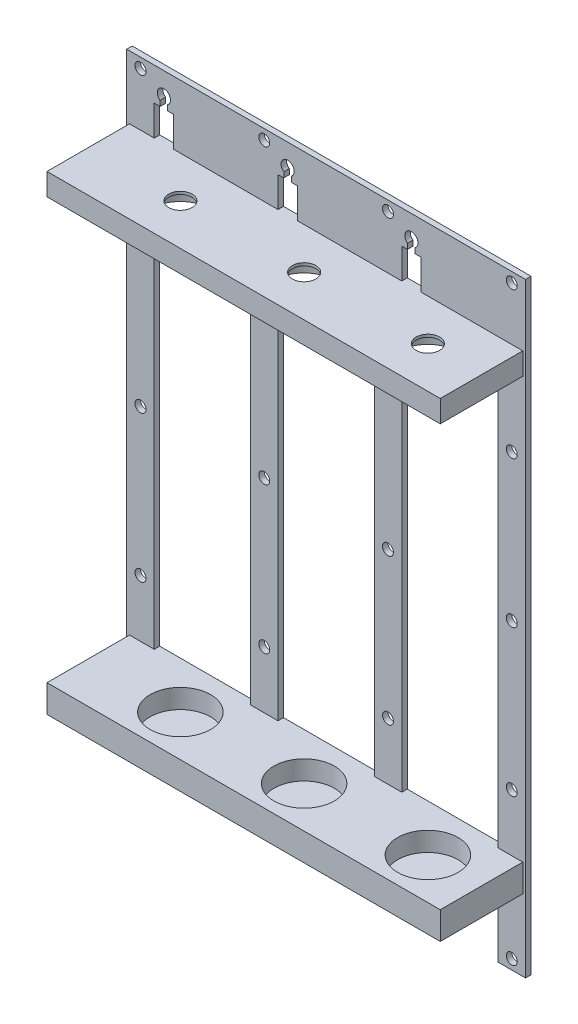
SolidWorks part; units mm, degrees
ref_plane "Płaszczyzna przednia" through (0, 0, 0) normal (0, 0, 1) x (1, 0, 0)
ref_plane "Płaszczyzna górna" through (0, 0, 0) normal (0, 1, 0) x (1, 0, 0)
ref_plane "Płaszczyzna prawa" through (0, 0, 0) normal (1, 0, 0) x (0, 0, -1)
sketch "Szkic4" plane through (0, 0, 0) normal (0, 0, 1) x (1, 0, 0)
  line L14 (-48.2384, -12) -> (-48.2384, -10.0494)
  line L15 (-46.1384, -12) -> (-48.2384, -12)
  line L32 (71.8616, -220) -> (81.8616, -220)
  line L33 (81.8616, -220) -> (81.8616, 0)
  line L34 (81.8616, 0) -> (-63.1384, 0)
  line L35 (-63.1384, 0) -> (-63.1384, -220)
  line L36 (-63.1384, -220) -> (-53.1384, -220)
  line L37 (-53.1384, -220) -> (-53.1384, -31)
  line L38 (-53.1384, -31) -> (-18.1384, -31)
  line L39 (-18.1384, -31) -> (-18.1384, -220)
  line L40 (-18.1384, -220) -> (-8.1384, -220)
  line L41 (-8.1384, -220) -> (-8.1384, -31)
  line L42 (-8.1384, -31) -> (26.8616, -31)
  line L43 (26.8616, -31) -> (26.8616, -220)
  line L44 (26.8616, -220) -> (36.8616, -220)
  line L45 (36.8616, -220) -> (36.8616, -31)
  line L46 (36.8616, -31) -> (71.8616, -31)
  line L47 (71.8616, -31) -> (71.8616, -220)
  line L48 (-46.1384, -23) -> (-46.1384, -12)
  line L49 (-53.1384, -23) -> (-46.1384, -23)
  line L50 (-53.1384, -12) -> (-53.1384, -23)
  line L51 (-51.0384, -12) -> (-53.1384, -12)
  line L52 (-51.0384, -10.0494) -> (-51.0384, -12)
  line L60 (-3.2384, -12) -> (-3.2384, -10.0494)
  line L61 (-1.1384, -12) -> (-3.2384, -12)
  line L62 (-1.1384, -23) -> (-1.1384, -12)
  line L63 (-8.1384, -23) -> (-1.1384, -23)
  line L64 (-8.1384, -12) -> (-8.1384, -23)
  line L65 (-6.0384, -12) -> (-8.1384, -12)
  line L66 (-6.0384, -10.0494) -> (-6.0384, -12)
  line L74 (41.7616, -12) -> (41.7616, -10.0494)
  line L75 (43.8616, -12) -> (41.7616, -12)
  line L76 (43.8616, -23) -> (43.8616, -12)
  line L77 (36.8616, -23) -> (43.8616, -23)
  line L78 (36.8616, -12) -> (36.8616, -23)
  line L79 (38.9616, -12) -> (36.8616, -12)
  line L80 (38.9616, -10.0494) -> (38.9616, -12)
  arc A2 (-48.2384, -10.0494) -> (-51.0384, -10.0494) centre (-49.6384, -8.1) ccw
  arc A4 (-3.2384, -10.0494) -> (-6.0384, -10.0494) centre (-4.6384, -8.1) ccw
  arc A6 (41.7616, -10.0494) -> (38.9616, -10.0494) centre (40.3616, -8.1) ccw
  circle A8 centre (76.8616, -3.6) radius 2
  circle A10 centre (31.8616, -3.6) radius 2
  circle A12 centre (-13.1384, -3.6) radius 2
  circle A14 centre (-58.1384, -3.6) radius 2
  circle A16 centre (76.8616, -56.8) radius 2
  circle A18 centre (31.8616, -56.8) radius 2
  circle A20 centre (-13.1384, -56.8) radius 2
  circle A22 centre (76.8616, -110) radius 2
  circle A24 centre (31.8616, -110) radius 2
  circle A26 centre (-13.1384, -110) radius 2
  circle A28 centre (76.8616, -163.2) radius 2
  circle A30 centre (31.8616, -163.2) radius 2
  circle A32 centre (-13.1384, -163.2) radius 2
  circle A34 centre (76.8616, -216.4) radius 2
  circle A36 centre (31.8616, -216.4) radius 2
  circle A38 centre (-13.1384, -216.4) radius 2
  circle A40 centre (-58.1384, -56.8) radius 2
  circle A42 centre (-58.1384, -110) radius 2
  circle A44 centre (-58.1384, -163.2) radius 2
  circle A46 centre (-58.1384, -216.4) radius 2
extrude "Dodanie-wyciągnięcie1" add sketch "Szkic4" along normal blind 2
sketch "Szkic5" plane through (0, 0, 2) normal (0, 0, 1) x (1, 0, 0)
  line L0 (-63.1384, -220) -> (-63.1384, -185)
  line L1 (-63.1384, 0) -> (-63.1384, -220) construction
  line L2 (-63.1384, -185) -> (-63.1384, -192)
  line L3 (-63.1384, -185) -> (-63.1384, -184)
  line L4 (-63.1384, -192) -> (-63.1384, -194)
  line L5 (81.8616, -220) -> (81.8616, 0) construction
  line L6 (-63.1384, -184) -> (81.8616, -184)
  line L7 (-63.1384, -184) -> (-63.1384, -194)
  line L8 (-63.1384, -194) -> (81.8616, -194)
  line L9 (81.8616, -184) -> (81.8616, -194)
  dimension "D1" = 35
  dimension "D2" = 7
  dimension "D3" = 1
  dimension "D4" = 2
extrude "Dodanie-wyciągnięcie2" add sketch "Szkic5" along normal blind 30 contours L9 L6 L3 L0 L8 region at (9.3616, -189, 2)
sketch "Szkic6" plane through (0, 0, 2) normal (0, 0, -1) x (-1, 0, 0)
  line L0 (18.1384, -194) -> (53.1384, -194) construction
  line L1 (53.1384, -194) -> (53.1384, -184) construction
  line L2 (53.1384, -184) -> (18.1384, -184) construction
  line L3 (18.1384, -184) -> (18.1384, -194) construction
  line L4 (-26.8616, -194) -> (8.1384, -194) construction
  line L5 (8.1384, -194) -> (8.1384, -184) construction
  line L6 (8.1384, -184) -> (-26.8616, -184) construction
  line L7 (-26.8616, -184) -> (-26.8616, -194) construction
  line L8 (-36.8616, -184) -> (-71.8616, -184) construction
  line L9 (-71.8616, -184) -> (-71.8616, -194) construction
  line L10 (-71.8616, -194) -> (-36.8616, -194) construction
  line L11 (-36.8616, -194) -> (-36.8616, -184) construction
  line L12 (18.1384, -194) -> (53.1384, -194)
  line L13 (53.1384, -194) -> (53.1384, -184)
  line L14 (53.1384, -184) -> (18.1384, -184)
  line L15 (18.1384, -184) -> (18.1384, -194)
  line L16 (-26.8616, -194) -> (8.1384, -194)
  line L17 (8.1384, -194) -> (8.1384, -184)
  line L18 (8.1384, -184) -> (-26.8616, -184)
  line L19 (-26.8616, -184) -> (-26.8616, -194)
  line L20 (-36.8616, -184) -> (-71.8616, -184)
  line L21 (-71.8616, -184) -> (-71.8616, -194)
  line L22 (-71.8616, -194) -> (-36.8616, -194)
  line L23 (-36.8616, -194) -> (-36.8616, -184)
extrude "Dodanie-wyciągnięcie3" add sketch "Szkic6" along normal blind 2
sketch "Szkic7" plane through (0, -184, 0) normal (0, 1, 0) x (1, 0, 0)
  line L0 (-63.1384, -32) -> (-63.1384, -17)
  line L1 (-63.1384, -32) -> (-63.1384, -2) construction
  line L2 (-63.1384, -17) -> (-28.6384, -17)
  line L3 (-28.6384, -17) -> (16.3616, -17)
  line L4 (16.3616, -17) -> (61.3616, -17)
  circle A0 centre (61.3616, -17) radius 11
  circle A1 centre (16.3616, -17) radius 11
  circle A2 centre (-28.6384, -17) radius 11
  dimension "D5" = 22
  dimension "D6" = 22
  dimension "D7" = 22
  dimension "D1" = 15
  dimension "D2" = 34.5
  dimension "D3" = 45
  dimension "D4" = 45
extrude "Wytnij-wyciągnięcie1" cut sketch "Szkic7" against normal blind 7 contours A0
extrude "Wytnij-wyciągnięcie2" cut sketch "Szkic7<4>" against normal blind 7 contours A1
sketch "Szkic7<4>" plane through (0, -184, 0) normal (0, 1, 0) x (1, 0, 0) same geometry as "Szkic7"
extrude "Wytnij-wyciągnięcie3" cut sketch "Szkic7<5>" against normal blind 7 contours A2
sketch "Szkic7<5>" plane through (0, -184, 0) normal (0, 1, 0) x (1, 0, 0) same geometry as "Szkic7"
sketch "Szkic9" plane through (0, -184, 0) normal (0, 1, 0) x (1, 0, 0)
  circle A0 centre (-28.6384, -17) radius 4.25
  circle A1 centre (16.3616, -17) radius 4.25
  circle A2 centre (61.3616, -17) radius 4.25
  dimension "D1" = 8.5
  dimension "D2" = 8.5
  dimension "D3" = 8.5
sketch "Szkic12" plane through (0, 0, 2) normal (0, 0, 1) x (1, 0, 0)
  line L0 (-63.1384, 0) -> (-63.1384, -184) construction
  line L1 (-63.1384, -31) -> (81.8616, -31)
  line L2 (-63.1384, -31) -> (-63.1384, -23)
  line L3 (-63.1384, -23) -> (81.8616, -23)
  line L4 (81.8616, -31) -> (81.8616, -23)
  line L5 (81.8616, -184) -> (81.8616, 0) construction
  line L6 (-53.1384, -31) -> (-18.1384, -31) construction
  dimension "D1" = 8
  dimension "D2" = 0
extrude "Dodanie-wyciągnięcie5" add sketch "Szkic12" along normal up to surface (30 mm away) and the other way up to surface (2 mm away) up to face at (9.3616, -189, 32) other way up to face at (9.3616, -182.75, 0)
sketch "Szkic13" plane through (0, -31, 0) normal (0, -1, 0) x (1, 0, 0)
  circle A6 centre (61.3616, 17) radius 4.25
  circle A7 centre (61.3616, 17) radius 11
  circle A8 centre (16.3616, 17) radius 4.25
  circle A9 centre (16.3616, 17) radius 11
  circle A10 centre (-28.6384, 17) radius 4.25
  circle A11 centre (-28.6384, 17) radius 11
extrude "Wytnij-wyciągnięcie9" cut sketch "Szkic13" against normal blind 59 contours A6 | A10 | A8
extrude "Wytnij-wyciągnięcie10" cut sketch "Szkic13<3>" against normal blind 7 contours A7 | A9 | A11
sketch "Szkic13<3>" plane through (0, -31, 0) normal (0, -1, 0) x (1, 0, 0) same geometry as "Szkic13"
sketch "Szkic14" plane through (0, -194, 0) normal (0, -1, 0) x (1, 0, 0)
  line L0 (-63.1384, 2) -> (-62.1384, 2)
  line L1 (-63.1384, 2) -> (-53.1384, 2) construction
  line L2 (-62.1384, 2) -> (-62.1384, 31)
  line L4 (80.8616, 31) -> (80.8616, 2)
  line L5 (71.8616, 2) -> (81.8616, 2) construction
  line L6 (80.8616, 2) -> (81.8616, 2)
  line L7 (81.8616, 32) -> (81.8616, 2) construction
  line L9 (-63.1384, 2) -> (-63.1384, 32)
  line L11 (81.8616, 32) -> (81.8616, 2)
  line L12 (-62.1384, 31) -> (-62.1384, 32)
  line L13 (80.8616, 31) -> (80.8616, 32)
  line L14 (81.8616, 32) -> (80.8616, 32)
  line L15 (-63.1384, 32) -> (-62.1384, 32)
  dimension "D1" = 1
  dimension "D3" = 1
extrude "Wytnij-wyciągnięcie11" cut sketch "Szkic14" against normal blind 178
